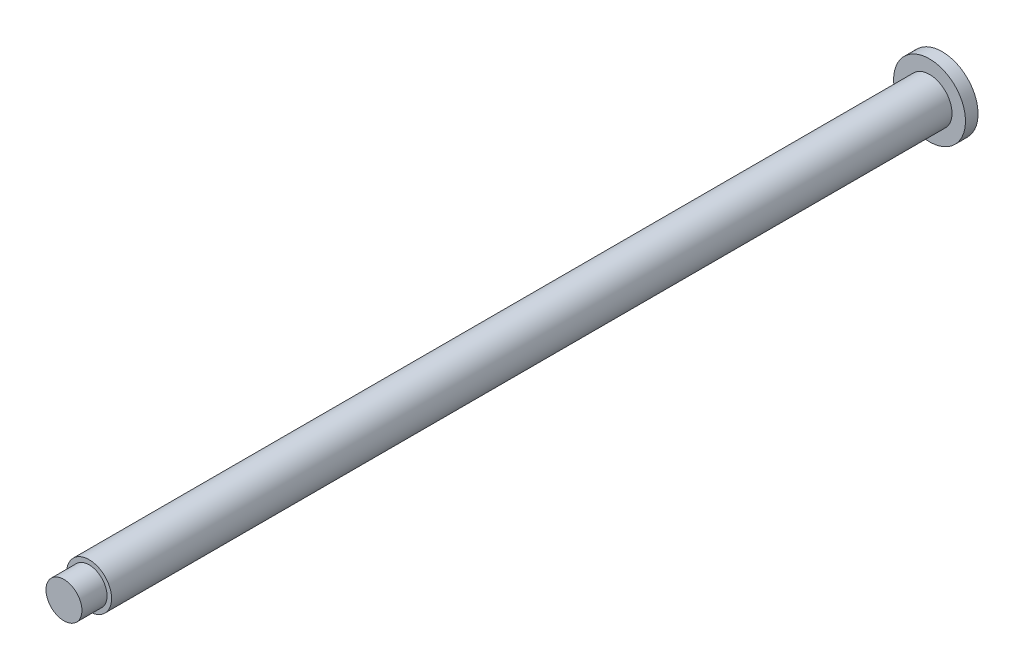
SolidWorks part; units mm, degrees
ref_plane "Front Plane" through (0, 0, 0) normal (1, 0, 0) x (0, 1, 0)
ref_plane "Top Plane" through (0, 0, 0) normal (0, 0, 1) x (0, 1, 0)
ref_plane "Right Plane" through (0, 0, 0) normal (0, 1, 0) x (-1, 0, 0)
sketch "Sketch1" plane through (0, 0, 0) normal (0, 0, 1) x (0, 1, 0)
  circle A0 centre (0, 0) radius 2.5
extrude "Boss-Extrude1" add sketch "Sketch1" along normal blind 93.5 contours A0
sketch "Sketch2" plane through (0, 0, 0) normal (0, 0, -1) x (1, 0, 0)
  circle A0 centre (0, 0) radius 4
extrude "Boss-Extrude2" add sketch "Sketch2" along normal blind 1.4
sketch "Sketch3" plane through (0, 0, -1.4) normal (0, 0, -1) x (1, 0, 0)
  circle A0 centre (0, 0) radius 2.05
extrude "Cut-Extrude1" cut sketch "Sketch3" against normal blind 3
sketch "Sketch4" plane through (0, 0, 93.5) normal (0, 0, 1) x (1, 0, 0)
  circle A0 centre (0, 0) radius 2
extrude "Boss-Extrude3" add sketch "Sketch4" along normal blind 2.8
equation "\"whitekey_cutout_length\"= 101.5"
equation "\"key_mount_recess_length\"=50"
equation "\"key_mount_recess_height\"=12.5"
equation "\"key_mount_recess_depth\"=1.5"
equation "\"wall_thickness\"=10"
equation "\"guide_brace_height\"=20"
equation "\"guide_brace_thickness\"=2"
equation "\"dowel_recess_depth\"=9"
equation "\"dowel_recess_offset\"=3"
equation "\"base_mount_height\"=40"
equation "\"base_rear_length\"=80"
equation "\"base_front_length\"=111.5"
equation "\"screw_hole_wall_offset\"=7.25"
equation "\"screw_hole_edge_inset\"=4.5"
equation "\"screw_hole_diameter\"=3.8"
equation "\"screw_head_hole_diameter\"=6.7"
equation "\"screw_nut_hole_side_len\"=3.5"
equation "\"screw_nut_recess_offset\"=0.3"
equation "\"screw_head_and_nut_recess_depth\"=2.5"
equation "\"screw_shaft_diameter\"=3.5"
equation "\"switch_board_width\"=30"
equation "\"switch_board_wall_offset\"=11.5"
equation "\"heatset_insert_hole_diameter\"=4.8"
equation "\"heatset_insert_hole_depth\"=3.8"
equation "\"front_rear_panel_width\"=23.75"
equation "\"rod_length_adj\"=0.5"
equation "\"rod_insert_length\"=2.8"
equation "\"D1@Boss-Extrude3\"=\"rod_insert_length\""
equation "\"D1@Boss-Extrude2\"=2-\"rod_length_adj\"-0.1"
equation "\"D1@Boss-Extrude1\"=\"rod_length_adj\"+93.00mm"
